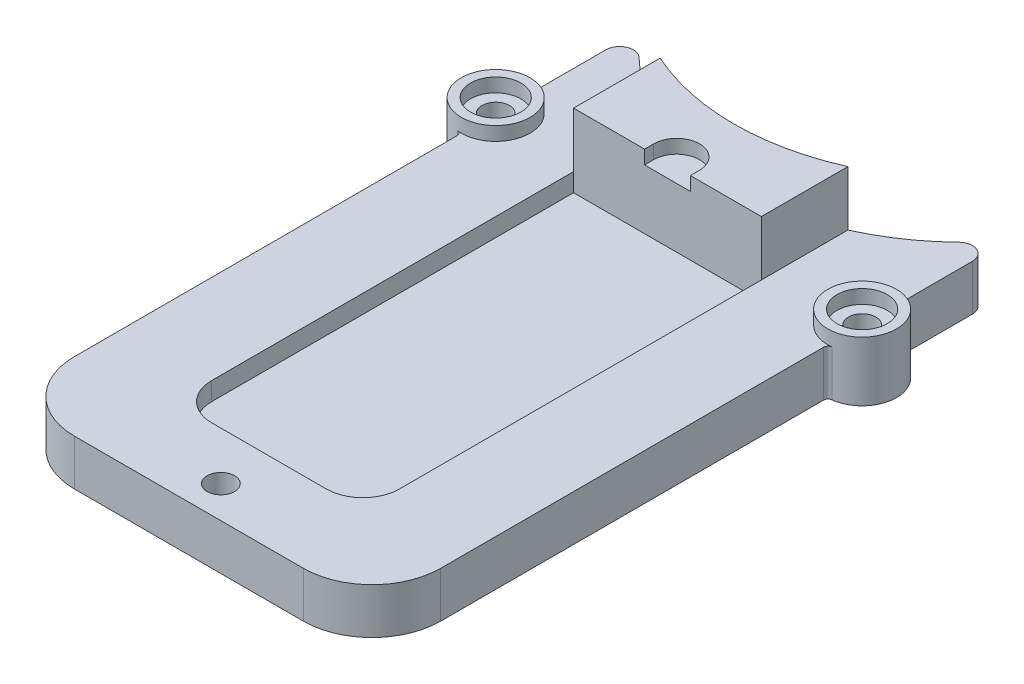
SolidWorks part; units mm, degrees
ref_plane "Front Plane" through (0, 0, 0) normal (0, 0, 1) x (1, 0, 0)
ref_plane "Top Plane" through (0, 0, 0) normal (0, 1, 0) x (1, 0, 0)
ref_plane "Right Plane" through (0, 0, 0) normal (1, 0, 0) x (0, 0, -1)
sketch "Sketch1" plane through (0, 0, 0) normal (0, 1, 0) x (1, 0, 0)
  line L0 (0, 0) -> (0, -110.4541) construction
  line L1 (25, -169) -> (-25, -169)
  line L2 (-40, -154) -> (-40, -37.9473)
  line L3 (40, -154) -> (40, -37.9473)
  arc A1 (-25, -169) -> (-40, -154) centre (-25, -154) cw
  arc A2 (25, -169) -> (40, -154) centre (25, -154) ccw
  arc A3 (-40, -37.9473) -> (-34.9057, -35.7994) centre (-37, -37.9473) cw
  arc A4 (40, -37.9473) -> (34.9057, -35.7994) centre (37, -37.9473) ccw
  arc A5 (-34.9057, -35.7994) -> (34.9057, -35.7994) centre (0, 0) ccw
  point P7 (0, -169)
  dimension "D1" = 50
  dimension "D2" = 3
  dimension "D3" = 15
  dimension "D4" = 80
  dimension "D5" = 119
extrude "Boss-Extrude1" add sketch "Sketch1" along normal blind 10
sketch "Sketch2" plane through (0, 0, 0) normal (0, 1, 0) x (1, 0, 0)
  line L0 (0, 0) -> (0, -114.9769) construction
  line L1 (40, -154) -> (40, -37.9473) construction
  line L2 (-25, -169) -> (25, -169) construction
  circle A0 centre (40, -62) radius 7.5
  dimension "D1" = 7.5
  dimension "D2" = 107
extrude "Boss-Extrude2" add sketch "Sketch2" along normal blind 13 contours A0
sketch "Sketch3" plane through (0, 10, 0) normal (0, 1, 0) x (1, 0, 0)
  line L0 (-25, -169) -> (25, -169) construction
  line L2 (-20.5, -45.6043) -> (-20.5, -64.5)
  line L3 (-20.5, -64.5) -> (20.5, -64.5)
  line L4 (20.5, -45.6043) -> (20.5, -64.5)
  line L5 (0, 0) -> (0, -129) construction
  arc A0 (-34.9057, -35.7994) -> (34.9057, -35.7994) centre (0, 0) ccw construction
  arc A1 (-20.5, -45.6043) -> (20.5, -45.6043) centre (0, 0) ccw
  point P0 (0, -50)
  point P2 (0, -64.5)
  dimension "D1" = 104.5
  dimension "D2" = 41
extrude "Boss-Extrude3" add sketch "Sketch3" along normal blind 12
sketch "Sketch4" plane through (0, 10, 0) normal (0, 1, 0) x (1, 0, 0)
  line L1 (-20.5, -64.5) -> (20.5, -64.5)
  line L2 (-20.5, -64.5) -> (-20.5, -151.5)
  line L3 (-20.5, -151.5) -> (20.5, -151.5)
  line L4 (20.5, -64.5) -> (20.5, -151.5)
  dimension "D1" = 87
  dimension "D2" = 41
extrude "Cut-Extrude1" cut sketch "Sketch4" against normal blind 4
sketch "Sketch5" plane through (0, 22, 0) normal (0, 1, 0) x (1, 0, 0)
  line L0 (-5, -64.5) -> (-5, -62.5)
  line L1 (-20.5, -64.5) -> (20.5, -64.5) construction
  line L2 (5, -62.5) -> (5, -64.5)
  line L3 (5, -64.5) -> (-5, -64.5)
  arc A0 (-5, -62.5) -> (5, -62.5) centre (0, -62.5) cw
  point P6 (0, -64.5)
  dimension "D1" = 5
  dimension "D2" = 2
extrude "Cut-Extrude2" cut sketch "Sketch5" against normal blind 3
hole_wizard "CBORE for M5 Hex Head Bolt1" positions "Sketch6" profile "Sketch7" counterbore size "M5" standard "ANSI Metric" end condition through all
sketch "Sketch6" plane through (0, 13, 0) normal (0, 1, 0) x (1, 0, 0)
  point P0 (40, -62)
sketch "Sketch7" plane through (40, 13, 62) normal (1, 0, 0) x (0, 0, 1)
  line L0 (0, 0) -> (0, 13)
  line L1 (0, 13) -> (3, 13)
  line L3 (3, 13) -> (3, 3)
  line L4 (3, 3) -> (5.5, 3)
  line L5 (5.5, 3) -> (5.5, 0)
  line L7 (5.5, 0) -> (0, 0)
  line L11 (0, -6.35) -> (0, 107.95) construction
  dimension "Thru Hole Dia." = 6
  dimension "Thru Hole Depth" = 13
  dimension "C'Bore Dia." = 11
  dimension "C'Bore Depth" = 3
mirror "Mirror3" about plane through (0, 0, 0) normal (1, 0, 0) of "CBORE for M5 Hex Head Bolt1", "Boss-Extrude2"
sketch "Sketch8" plane through (0, 10, 0) normal (0, 1, 0) x (1, 0, 0)
  line L0 (-25, -169) -> (25, -169) construction
  circle A0 centre (0, -162) radius 3
  dimension "D1" = 6
  dimension "D2" = 7
extrude "Cut-Extrude3" cut sketch "Sketch8" against normal through all
fillet "Fillet1" radius 8 2 edges at (20.5, 8, 151.5) (-20.5, 8, 151.5)
fillet "Fillet2" radius 1 4 edges at (-40, 5, 69.5) (-40, 5, 54.5) (40, 5, 54.5) (40, 5, 69.5)
